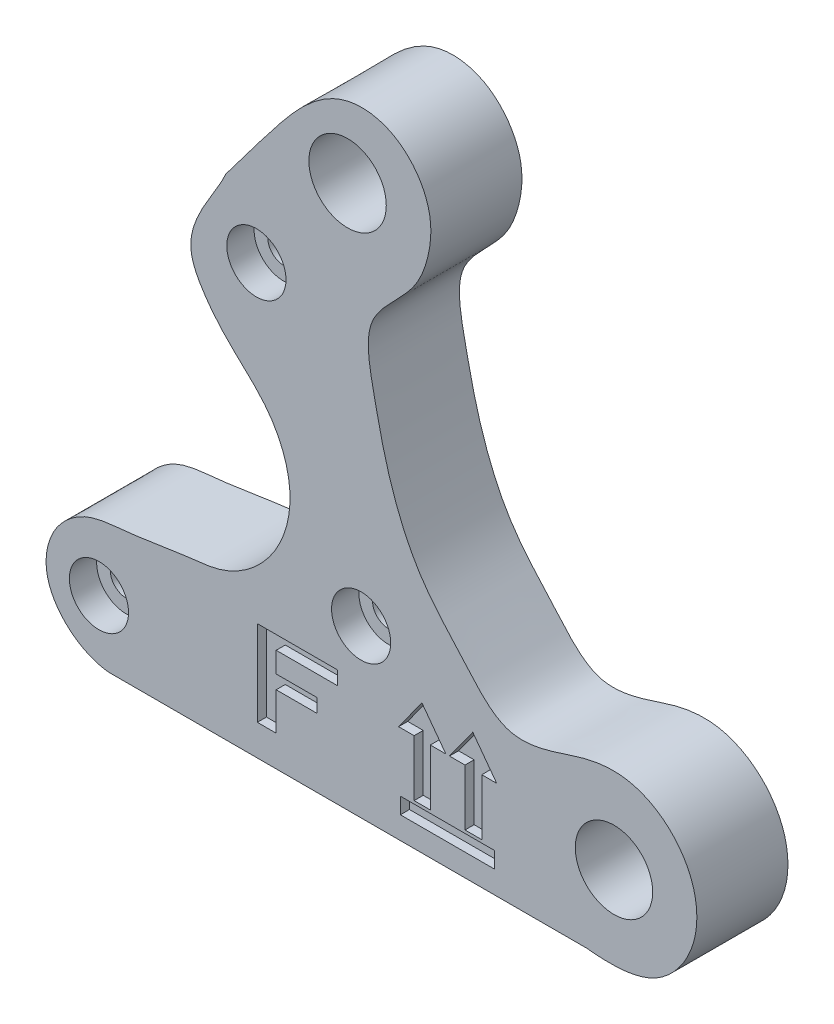
SolidWorks part; units mm, degrees
ref_plane "Piano frontale" through (0, 0, 0) normal (0, 0, 1) x (1, 0, 0)
ref_plane "Piano superiore" through (0, 0, 0) normal (0, 1, 0) x (1, 0, 0)
ref_plane "Piano destro" through (0, 0, 0) normal (1, 0, 0) x (0, 0, -1)
sketch "Model" plane through (0, 0, 0) normal (0, 0, 1) x (1, 0, 0)
  line L0 (22.0868, -27.7982) -> (-30.3742, -27.7982)
  line L1 (-13.8722, 30.8613) -> (-17.5384, 26.0041)
  line L3 (-12.014, -24.4034) -> (-12.014, -20.2736)
  line L4 (-12.014, -20.2736) -> (-7.5087, -20.2736)
  line L5 (-7.5087, -20.2736) -> (-7.5087, -18.7718)
  line L6 (-7.5087, -18.7718) -> (-12.014, -18.7718)
  line L7 (-12.014, -18.7718) -> (-12.014, -16.5192)
  line L8 (-12.014, -16.5192) -> (-5.2561, -16.5192)
  line L9 (-5.2561, -16.5192) -> (-5.2561, -15.0175)
  line L10 (-5.2561, -15.0175) -> (-14.0789, -15.0175)
  line L11 (-14.0789, -15.0175) -> (-14.0789, -24.4034)
  line L12 (-14.0789, -24.4034) -> (-12.014, -24.4034)
  line L13 (11.9389, -25.342) -> (11.9389, -23.568)
  line L14 (11.9389, -23.568) -> (1.6238, -23.568)
  line L15 (1.6238, -23.568) -> (1.6238, -25.342)
  line L16 (1.6238, -25.342) -> (11.9389, -25.342)
  line L17 (3.1349, -17.0636) -> (3.1349, -23.2395)
  line L18 (3.1349, -23.2395) -> (4.9088, -23.2395)
  line L19 (4.9088, -23.2395) -> (4.9088, -17.0636)
  line L20 (4.9088, -17.0636) -> (6.6171, -17.0636)
  line L21 (6.6171, -17.0636) -> (3.989, -13.5157)
  line L22 (3.989, -13.5157) -> (1.4267, -17.0636)
  line L23 (1.4267, -17.0636) -> (3.1349, -17.0636)
  line L24 (8.7195, -17.0636) -> (8.7195, -23.2395)
  line L25 (8.7195, -23.2395) -> (10.5592, -23.2395)
  line L26 (10.5592, -23.2395) -> (10.5592, -17.0636)
  line L27 (10.5592, -17.0636) -> (12.2017, -17.0636)
  line L28 (12.2017, -17.0636) -> (9.5736, -13.5157)
  line L29 (9.5736, -13.5157) -> (7.0113, -17.0636)
  line L30 (7.0113, -17.0636) -> (8.7195, -17.0636)
  line L33 (-14.1862, 19.2414) -> (-2.6848, -9.5461) construction
  line L34 (-14.1862, 19.2414) -> (-42.9737, 7.74) construction
  line L35 (-2.6848, -9.5461) -> (-31.4723, -21.0474) construction
  line L36 (-42.9737, 7.74) -> (-31.4723, -21.0474) construction
  circle A0 centre (-31.4723, -21.0474) radius 3.25
  circle A1 centre (-31.4723, -21.0474) radius 1.75
  circle A2 centre (25.0764, -18.8492) radius 4.25
  circle A3 centre (-4.1736, 31.8132) radius 4.25
  circle A4 centre (-14.1862, 19.2414) radius 3.25
  circle A5 centre (-14.1862, 19.2414) radius 1.75
  circle A6 centre (-2.6848, -9.5461) radius 3.25
  circle A7 centre (-2.6848, -9.5461) radius 1.75
  spline S0 degree 3 poles (-17.5384, 26.0041) (-18.5383, 23.6059) (-22.9066, 18.7541) (-19.9898, 13.3732) (-17.0183, 9.6824) (-12.1971, 5.9861) (-9.6734, -1.214) (-12.0562, -8.3476) (-17.1104, -12.0777) (-21.535, -12.4287) (-24.918, -12.9763) (-28.5888, -13.5171) (-32.9532, -13.7948) (-36.7404, -16.8305) (-38.1891, -23.6168) (-33.4872, -27.5208) (-30.3742, -27.7982) knots 0 0 0 0 0.128042 0.173454 0.219153 0.309797 0.399283 0.488821 0.578317 0.618189 0.656227 0.708612 0.759756 0.819423 0.878795 1 1 1 1
  spline S1 degree 3 poles (-13.8722, 30.8613) (-11.2429, 34.1378) (-7.15, 40.5202) (1.5622, 39.4164) (5.3459, 34.5588) (4.8684, 29.2717) (2.8695, 24.3539) (-2.7703, 20.7069) (-1.1921, 12.6631) (0.3338, 5.6041) (3.5533, -1.8737) (8.439, -6.9293) (12.7007, -12.1075) (18.0194, -11.2219) (21.8807, -9.6806) (26.2361, -9.1685) (30.7504, -10.9935) (34.1244, -15.3044) (34.5217, -21.8166) (29.9397, -28.1652) (24.4483, -28.0456) (22.0868, -27.7982) knots 0 0 0 0 0.113777 0.147278 0.205992 0.245683 0.275494 0.337832 0.391118 0.459762 0.52599 0.587795 0.640879 0.676387 0.7119 0.747233 0.782557 0.829334 0.876114 0.937741 1 1 1 1
  point P0 (25.0764, -18.8492)
  dimension "D4" = 8.5
  dimension "D5" = 3.5
  dimension "D6" = 6.5
  dimension "D1" = 8.5
  dimension "D3" = 31
extrude "Main body" add sketch "Model" against normal blind 10 contours S0 L0 S1 L1 | A5 | A3 | A7 | A1 | A2
extrude "Symbols" cut sketch "Model<5>" against normal blind 1 contours L11 L12 L3 L4 L5 L6 L7 L8 L9 L10 | L22 L23 L17 L18 L19 L20 L21 | L15 L16 L13 L14 | L29 L30 L24 L25 L26 L27 L28 region at (-13.0464, -24.2746, 0) region at (6.7813, -24.455, 0) region at (4.0169, -18.2014, 0) region at (9.6197, -18.2399, 0)
sketch "Model<5>" plane through (0, 0, 0) normal (0, 0, 1) x (1, 0, 0) same geometry as "Model"
extrude "Recess holes" cut sketch "Model<6>" against normal blind 3 contours A4 A5 | A0 A1 | A6 A7 | A0 A1 | A6 A7 | A4 A5 region at (-34.6304, -21.0474, 0) region at (-17.3443, 19.2414, 0) region at (-5.8429, -9.5461, 0)
sketch "Model<6>" plane through (0, 0, 0) normal (0, 0, 1) x (1, 0, 0) same geometry as "Model"
ref_axis "Rod1 axis" through (-4.1736, 31.8132, -10) along (0, 0, 1)
ref_axis "Motor screw 1" through (-31.4723, -21.0474, -10) along (0, 0, 1)
ref_axis "Motor screw 2" through (-2.6848, -9.5461, -10) along (0, 0, 1)
ref_axis "Motor screw 3" through (-14.1862, 19.2414, -10) along (0, 0, 1)
